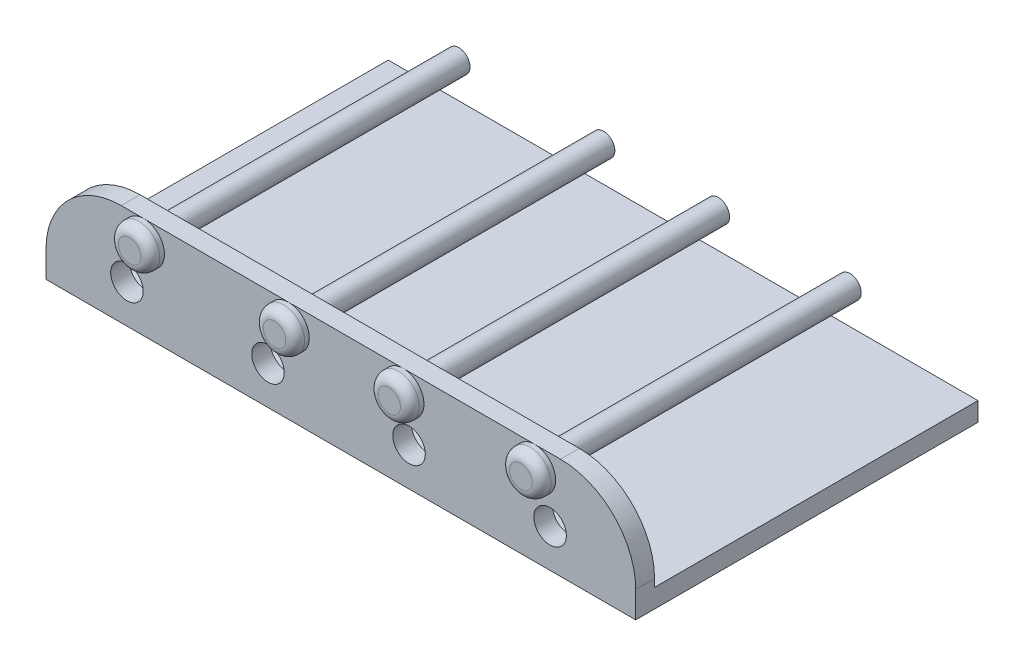
SolidWorks part; units mm, degrees
ref_plane "Front Plane" through (0, 0, 0) normal (0, 0, 1) x (1, 0, 0)
ref_plane "Top Plane" through (0, 0, 0) normal (0, 1, 0) x (1, 0, 0)
ref_plane "Right Plane" through (0, 0, 0) normal (1, 0, 0) x (0, 0, -1)
sketch "Sketch1" plane through (0, 0, 0) normal (0, 1, 0) x (1, 0, 0)
  line L1 (0, 0) -> (79.6544, 0)
  line L2 (0, 0) -> (0, 46.228)
  line L3 (0, 46.228) -> (79.6544, 46.228)
  line L4 (79.6544, 0) -> (79.6544, 46.228)
  dimension "D1" = 46.228
  dimension "D2" = 79.6544
extrude "Boss-Extrude1" add sketch "Sketch1" along normal blind 2.54
sketch "Sketch2" plane through (79.6544, 0, 0) normal (1, 0, 0) x (0, 0, -1)
  line L0 (0, 2.54) -> (0, 13.716)
  line L1 (0, 13.716) -> (2.54, 13.716)
  line L2 (2.54, 13.716) -> (2.54, 2.54)
  line L3 (0, 2.54) -> (46.228, 2.54) construction
  line L4 (2.54, 2.54) -> (0, 2.54)
  dimension "D1" = 2.54
  dimension "D2" = 11.176
extrude "Boss-Extrude2" add sketch "Sketch2" against normal up to surface (79.6544 mm away) up to face at (0, 1.27, -23.114)
sketch "Sketch3" plane through (0, 0, 0) normal (0, 0, 1) x (1, 0, 0)
  line L1 (0, 13.716) -> (79.6544, 13.716) construction
  line L2 (0, 13.716) -> (0, 0) construction
  circle A0 centre (10.9347, 5.1689) radius 2.1971
  circle A1 centre (29.9847, 5.1689) radius 2.1971
  circle A2 centre (49.0347, 5.1689) radius 2.1971
  circle A3 centre (68.0847, 5.1689) radius 2.1971
  point P9 (10.9347, 7.366)
  point P11 (8.7376, 5.1689)
  point P22 (18.6939, 10.8162)
  point P23 (20.0788, 11.4048)
  dimension "D1" = 4.3942
  dimension "D3" = 38.1
  dimension "D4" = 57.15
  dimension "D2" = 19.05
  dimension "D5" = 6.35
  dimension "D6" = 8.7376
extrude "Cut-Extrude1" cut sketch "Sketch3" against normal through all
sketch "Sketch4" plane through (0, 0, 0) normal (0, 0, 1) x (1, 0, 0)
  line L0 (0, 13.716) -> (0, 0) construction
  line L1 (0, 13.716) -> (79.6544, 13.716) construction
  circle A0 centre (13.208, 10.922) radius 2.794
  circle A1 centre (32.766, 10.922) radius 2.794
  circle A2 centre (48.26, 10.922) radius 2.794
  circle A3 centre (66.04, 10.922) radius 2.794
  point P9 (16.002, 10.922)
  point P11 (35.56, 10.922)
  point P15 (0, 0)
  point P16 (13.208, 8.128)
  dimension "D1" = 5.588
  dimension "D2" = 16.002
  dimension "D3" = 35.56
  dimension "D4" = 5.588
  dimension "D5" = 48.26
  dimension "D6" = 66.04
extrude "Boss-Extrude3" add sketch "Sketch4" along normal blind 1.905
fillet "Fillet1" radius 10.16 2 edges at (79.6544, 13.716, -1.27) (0, 13.716, -1.27)
fillet "Fillet2" radius 1.27 4 edges at (68.834, 10.922, 1.905) (51.054, 10.922, 1.905) (35.56, 10.922, 1.905) (16.002, 10.922, 1.905)
sketch "Sketch5" plane through (0, 0, -2.54) normal (0, 0, -1) x (-1, 0, 0)
  circle A0 centre (-66.04, 10.922) radius 1.524
  circle A1 centre (-48.26, 10.922) radius 1.524
  circle A2 centre (-32.766, 10.922) radius 1.524
  circle A3 centre (-13.208, 10.922) radius 1.524
  circle A4 centre (-66.04, 10.922) radius 2.794 construction
  circle A5 centre (-48.26, 10.922) radius 2.794 construction
  circle A6 centre (-32.766, 10.922) radius 2.794 construction
  circle A7 centre (-13.208, 10.922) radius 2.794 construction
  dimension "D1" = 3.048
extrude "Boss-Extrude4" add sketch "Sketch5" along normal offset from surface (40.005 mm away) 44.45 up to face at (67.564, 10.922, 1.905)
